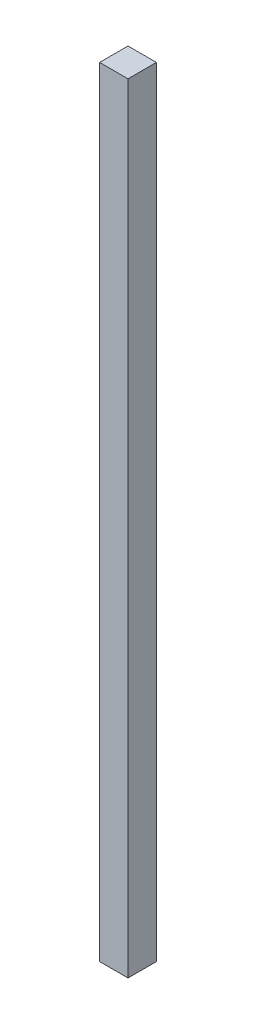
SolidWorks part; units mm, degrees
ref_plane "Plan de face" through (0, 0, 0) normal (0, 0, 1) x (1, 0, 0)
ref_plane "Plan de dessus" through (0, 0, 0) normal (0, 1, 0) x (1, 0, 0)
ref_plane "Plan de droite" through (0, 0, 0) normal (1, 0, 0) x (0, 0, -1)
sketch "Esquisse1" plane through (0, 0, 0) normal (0, 0, 1) x (1, 0, 0)
  line L1 (-51.4239, 37.1959) -> (-41.4239, 37.1959)
  line L2 (-51.4239, 37.1959) -> (-51.4239, -236.8041)
  line L3 (-51.4239, -236.8041) -> (-41.4239, -236.8041)
  line L4 (-41.4239, 37.1959) -> (-41.4239, -236.8041)
  dimension "D1" = 10
  dimension "D2" = 274
extrude "Boss.-Extru.1" add sketch "Esquisse1" along normal blind 10 contours L2 L3 L4 L1
equation "\"EpaisseurPlaque\"= 3"
equation "\"ProfondeurBoite\"=460"
equation "\"LongueurSyphon\"=170"
equation "\"LargeurSyphon\"=120"
equation "\"HauteurCoteDroit\"= 490"
equation "\"HauteurCoteGauche\"= 540"
equation "\"HauteurSolSyphon\"= 300"
equation "\"HauteurSyphon\"=\"HauteurCoteGauche\"-\"HauteurSolSyphon\""
equation "\"LargeurDroite\"=10"
equation "\"LargeurGauche\"=150"
equation "\"LargeurBoite\"= \"LargeurDroite\" + \"LargeurGauche\" + \"LargeurSyphon\""
equation "\"D2@Esquisse1\"=\"HauteurCoteGauche\" - \"HauteurSyphon\" - 20 - 6"
